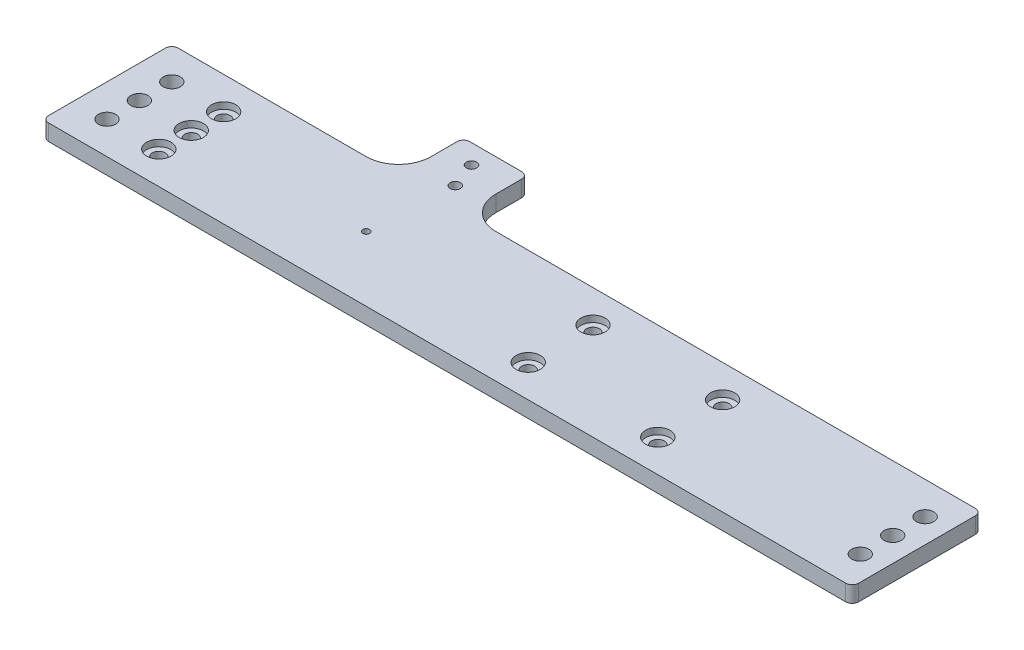
SolidWorks part; units mm, degrees
material "6061-T6 (SS)"
ref_plane "Front" through (0, 0, 0) normal (0, 0, 1) x (1, 0, 0)
ref_plane "Top" through (0, 0, 0) normal (0, 1, 0) x (1, 0, 0)
ref_plane "Right" through (0, 0, 0) normal (1, 0, 0) x (0, 0, -1)
sketch "Sketch1" plane through (0, 0, 0) normal (0, 1, 0) x (1, 0, 0)
  line L1 (-158.75, -25.4) -> (158.75, -25.4)
  line L2 (-158.75, -25.4) -> (-158.75, 25.4)
  line L3 (-158.75, 25.4) -> (158.75, 25.4)
  line L4 (158.75, -25.4) -> (158.75, 25.4)
  line L5 (-158.75, -25.4) -> (158.75, 25.4) construction
  line L6 (-158.75, 25.4) -> (158.75, -25.4) construction
  point P0 (0, 0)
  dimension "D1" = 50.8
  dimension "D2" = 317.5
extrude "Boss-Extrude1" add sketch "Sketch1" along normal blind 6.35
hole_wizard "CBORE for #10 Socket Head Cap Screw1" positions "Sketch2" profile "Sketch4" counterbore size "#10" standard "ANSI Inch" end condition through all
sketch "Sketch2" plane through (0, 6.35, 0) normal (0, 1, 0) x (1, 0, 0)
  line L2 (158.75, 25.4) -> (-158.75, 25.4) construction
  line L6 (-158.75, -25.4) -> (158.75, -25.4) construction
  line L8 (-158.75, 25.4) -> (-158.75, -25.4) construction
  line L12 (158.75, -25.4) -> (158.75, 25.4) construction
  line L15 (19.05, 12.7) -> (19.05, 25.4) construction
  line L17 (19.05, -12.7) -> (19.05, -25.4) construction
  line L18 (-125.73, -25.4) -> (-125.73, -12.7) construction
  line L20 (-125.73, 0) -> (-125.73, 12.7) construction
  line L21 (-125.73, 12.7) -> (-125.73, 25.4) construction
  line L22 (-125.73, 0) -> (-125.73, -12.7) construction
  point P64 (19.05, 12.7)
  point P66 (69.85, 12.7)
  point P68 (19.05, -12.7)
  point P70 (69.85, -12.7)
  point P92 (-125.73, 12.7)
  point P94 (-125.73, 0)
  point P102 (-125.73, -12.7)
  dimension "D2" = 50.8
  dimension "D3" = 25.4
  dimension "D4" = 88.9
  dimension "D5" = 33.02
sketch "Sketch4" plane through (-125.73, 6.35, 12.7) normal (1, 0, 0) x (0, 0, 1)
  line L0 (0, 0) -> (0, 6.35)
  line L1 (0, 6.35) -> (2.5527, 6.35)
  line L3 (2.5527, 6.35) -> (2.5527, 2.54)
  line L4 (2.5527, 2.54) -> (4.7625, 2.54)
  line L5 (4.7625, 2.54) -> (4.7625, 0)
  line L7 (4.7625, 0) -> (0, 0)
  line L11 (0, -6.35) -> (0, 107.95) construction
  dimension "Thru Hole Dia." = 5.1054
  dimension "Thru Hole Depth" = 6.35
  dimension "C'Bore Dia." = 9.525
  dimension "C'Bore Depth" = 2.54
sketch "Sketch7" plane through (0, 0, 0) normal (0, -1, 0) x (1, 0, 0)
  line L0 (-146.05, 25.4) -> (-146.05, 12.7) construction
  line L1 (-158.75, 25.4) -> (158.75, 25.4) construction
  line L2 (-146.05, 12.7) -> (-146.05, 0) construction
  line L3 (-146.05, 0) -> (-146.05, -12.7) construction
  line L4 (-146.05, -12.7) -> (-146.05, -25.4) construction
  line L5 (158.75, -25.4) -> (-158.75, -25.4) construction
  line L7 (-158.75, -25.4) -> (-158.75, 25.4) construction
  line L8 (149.225, 25.4) -> (149.225, 12.7) construction
  line L9 (149.225, 12.7) -> (149.225, 0) construction
  line L10 (149.225, 0) -> (149.225, -12.7) construction
  line L11 (149.225, -12.7) -> (149.225, -25.4) construction
  line L13 (158.75, 25.4) -> (158.75, -25.4) construction
  point P0 (-146.05, 12.7)
  point P2 (-146.05, 0)
  point P4 (-146.05, -12.7)
  point P6 (149.225, 12.7)
  point P8 (149.225, 0)
  point P10 (149.225, -12.7)
  dimension "D1" = 12.7
  dimension "D2" = 9.525
hole_wizard "1/4 Clearance Hole2" positions "Sketch7" profile "Sketch6" hole size "1/4" standard "ANSI Inch" end condition through all
sketch "Sketch6" plane through (-146.05, 0, 12.7) normal (1, 0, 0) x (0, 0, -1)
  line L0 (0, 0) -> (0, 6.35)
  line L1 (0, 6.35) -> (3.3782, 6.35)
  line L2 (3.3782, 6.35) -> (3.3782, 0)
  line L5 (3.3782, 0) -> (0, 0)
  line L11 (0, -6.35) -> (0, 107.95) construction
  dimension "Thru Hole Dia." = 6.7564
  dimension "Thru Hole Depth" = 6.35
sketch "Sketch10" plane through (0, 0, 0) normal (0, -1, 0) x (-1, 0, 0)
  line L0 (158.75, 25.4) -> (158.75, -25.4) construction
  point P0 (57.15, 0)
  dimension "D1" = 101.6
hole_wizard "#6-32 Tapped Hole1" positions "Sketch10" profile "Sketch9" tap size "#6-32" standard "ANSI Inch" end condition through all
sketch "Sketch9" plane through (-57.15, 0, 0) normal (1, 0, 0) x (0, 0, -1)
  line L0 (0, 0) -> (0, 6.35)
  line L1 (0, 6.35) -> (1.3525, 6.35)
  line L2 (1.3525, 6.35) -> (1.3525, 0)
  line L5 (1.3525, 0) -> (0, 0)
  line L11 (0, -6.35) -> (0, 107.95) construction
  dimension "Thru Tap Drill Dia." = 2.7051
  dimension "Thru Tap Drill Depth" = 6.35
cosmetic thread "Hole Thread1" parameters "D2"=3.5052
sketch "Sketch11" plane through (0, 0, 0) normal (0, -1, 0) x (1, 0, 0)
  line L0 (158.75, -25.4) -> (-158.75, -25.4) construction
  line L1 (-70.0118, -25.4) -> (-48.1024, -25.4)
  line L2 (-70.0118, -25.4) -> (-70.0118, -45.81)
  line L3 (-70.0118, -45.81) -> (-48.1024, -45.81)
  line L4 (-48.1024, -25.4) -> (-48.1024, -45.81)
extrude "Boss-Extrude2" [suppressed] add sketch "Sketch11" against normal up to surface (6.35 mm away) up to face at (-57.15, 6.35, -1.3526)
sketch "Sketch12" plane through (0, 6.35, 0) normal (0, 1, 0) x (1, 0, 0)
  line L5 (-158.75, 25.4) -> (-158.75, -25.4) construction
  line L6 (-69.85, 25.4) -> (-69.85, 50.8)
  line L7 (158.75, 25.4) -> (-158.75, 25.4) construction
  line L8 (-69.85, 50.8) -> (-44.45, 50.8)
  line L9 (-44.45, 50.8) -> (-44.45, 25.4)
  line L10 (-69.85, 25.4) -> (-44.45, 25.4)
  dimension "D4" = 88.9
  dimension "D5" = 25.4
  dimension "D6" = 25.4
extrude "Boss-Extrude3" add sketch "Sketch12" against normal up to surface (6.35 mm away) up to face at (-57.15, 0, -1.3526)
sketch "Sketch15" plane through (0, 0, 0) normal (0, -1, 0) x (-1, 0, 0)
  point P0 (59.055, 43.18)
  point P3 (55.245, 33.02)
hole_wizard "#10-32 Tapped Hole1" positions "Sketch15" profile "Sketch14" tap size "#10-32" standard "ANSI Inch" end condition through all
sketch "Sketch14" plane through (-59.055, 0, -43.18) normal (1, 0, 0) x (0, 0, -1)
  line L0 (0, 0) -> (0, 6.35)
  line L1 (0, 6.35) -> (2.0193, 6.35)
  line L2 (2.0193, 6.35) -> (2.0193, 0)
  line L5 (2.0193, 0) -> (0, 0)
  line L11 (0, -6.35) -> (0, 107.95) construction
  dimension "Thru Tap Drill Dia." = 4.0386
  dimension "Thru Tap Drill Depth" = 6.35
fillet "Fillet1" radius 12.7 2 edges at (-44.45, 3.175, -25.4) (-69.85, 3.175, -25.4)
fillet "Fillet2" radius 2.54 6 edges at (158.75, 3.175, -25.4) (158.75, 3.175, 25.4) (-158.75, 3.175, 25.4) (-158.75, 3.175, -25.4) (-69.85, 3.175, -50.8) (-44.45, 3.175, -50.8)
